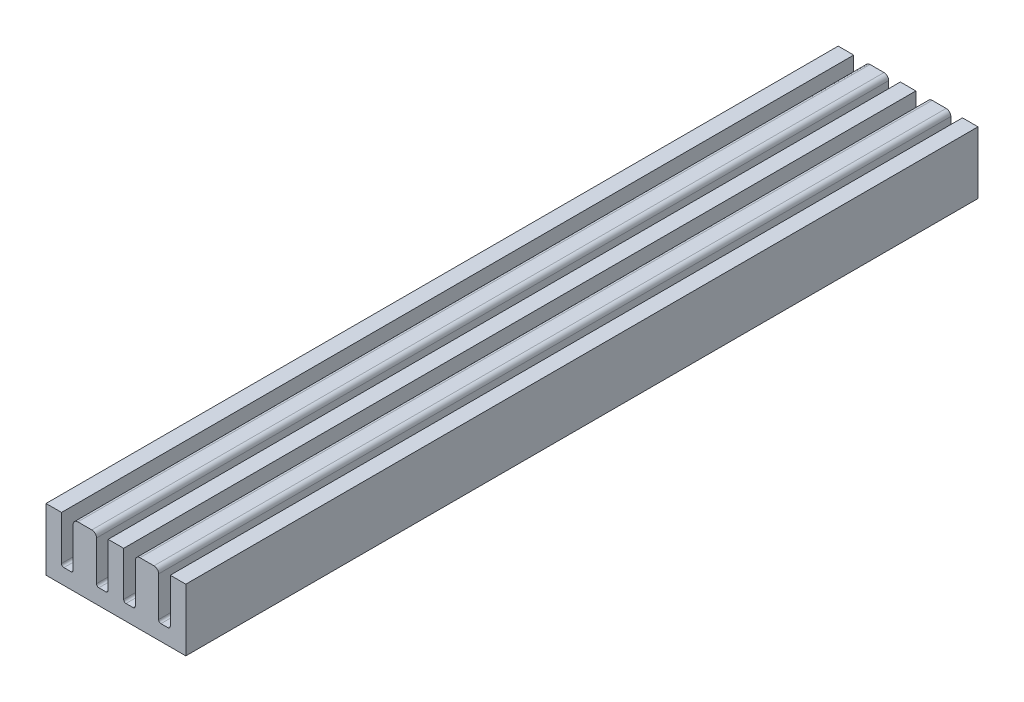
SolidWorks part; units mm, degrees
ref_plane "Plano frontal" through (0, 0, 0) normal (0, 0, 1) x (1, 0, 0)
ref_plane "Plano superior" through (0, 0, 0) normal (0, 1, 0) x (1, 0, 0)
ref_plane "Plano direito" through (0, 0, 0) normal (1, 0, 0) x (0, 0, -1)
sketch "Esboço1" plane through (0, 0, 0) normal (0, 0, 1) x (1, 0, 0)
  line L0 (-3.5, -37.8704) -> (-3.8019, -37.8704)
  line L1 (-2, -37.8704) -> (-2, -31.8704)
  line L2 (-3.5, -37.8704) -> (-5, -37.8704)
  line L3 (-0.5, -31.8704) -> (-3.5, -31.8704)
  line L4 (-2, -31.8704) -> (-2, -37.8704)
  line L5 (-0.5, -37.8704) -> (-3.5, -37.8704)
  line L6 (-3.5, -31.8704) -> (-3.5, -37.8704)
  line L7 (3, -37.8704) -> (1, -37.8704)
  line L8 (-2, -31.8704) -> (-2, -37.8704)
  line L9 (3, -31.8704) -> (3, -37.8704)
  line L10 (1, -31.8704) -> (3, -31.8704)
  line L11 (-3.5, -37.8704) -> (-3.5, -37.5685)
  line L12 (1, -37.8704) -> (1, -31.8704)
  line L13 (-5, -37.8704) -> (-5, -31.8704)
  line L14 (-5, -31.8704) -> (-7, -31.8704)
  line L15 (-7, -31.8704) -> (-7, -37.8704)
  line L16 (-7, -37.8704) -> (-5, -37.8704)
  line L17 (-0.5, -37.8704) -> (-0.5, -37.5685)
  line L18 (-0.5, -31.8704) -> (-0.5, -37.8704)
  line L19 (-0.5, -37.8704) -> (1, -37.8704)
  line L20 (-0.5, -37.8704) -> (-0.1981, -37.8704)
  line L22 (4.5, -37.8704) -> (4.1981, -37.8704)
  line L23 (4.5, -37.8704) -> (3, -37.8704)
  line L24 (4.5, -31.8704) -> (4.5, -37.8704)
  line L25 (4.5, -37.8704) -> (4.5, -37.5685)
  line L26 (11, -37.8704) -> (9, -37.8704)
  line L27 (11, -31.8704) -> (11, -37.8704)
  line L28 (9, -31.8704) -> (11, -31.8704)
  line L29 (9, -37.8704) -> (9, -31.8704)
  line L30 (7.5, -37.8704) -> (7.5, -37.5685)
  line L31 (6, -31.8704) -> (6, -37.8704)
  line L32 (7.5, -31.8704) -> (7.5, -37.8704)
  line L33 (4.5, -37.8704) -> (7.5, -37.8704)
  line L34 (6, -31.8704) -> (6, -37.8704)
  line L35 (4.5, -31.8704) -> (7.5, -31.8704)
  line L36 (7.5, -37.8704) -> (9, -37.8704)
  line L37 (6, -37.8704) -> (6, -31.8704)
  line L38 (7.5, -37.8704) -> (7.8019, -37.8704)
  line L39 (-7, -37.8704) -> (11, -37.8704)
  line L40 (-7, -37.8704) -> (-7, -39.8704)
  line L41 (-7, -39.8704) -> (11, -39.8704)
  line L42 (11, -37.8704) -> (11, -39.8704)
  arc A0 (-3.8019, -37.8704) -> (-3.5, -37.5685) centre (-3.8019, -37.5685) ccw
  arc A1 (0.6981, -37.8704) -> (1, -37.5685) centre (0.6981, -37.5685) ccw
  arc A2 (-4.6981, -37.8704) -> (-5, -37.5685) centre (-4.6981, -37.5685) cw
  arc A3 (-0.1981, -37.8704) -> (-0.5, -37.5685) centre (-0.1981, -37.5685) cw
  arc A4 (4.1981, -37.8704) -> (4.5, -37.5685) centre (4.1981, -37.5685) ccw
  arc A5 (8.6981, -37.8704) -> (9, -37.5685) centre (8.6981, -37.5685) ccw
  arc A6 (3.3019, -37.8704) -> (3, -37.5685) centre (3.3019, -37.5685) cw
  arc A7 (7.8019, -37.8704) -> (7.5, -37.5685) centre (7.8019, -37.5685) cw
  dimension "D1" = 1.5
  dimension "D2" = 2
  dimension "D4" = 2
  dimension "D5" = 1.5
  dimension "D6" = 6
extrude "Ressalto-extrusão1" add sketch "Esboço1" along normal blind 102 contours L3 L6 L5 L1 | L1 region at (-2.75, -34.8704, 0) region at (-1.25, -34.8704, 0)
extrude "Ressalto-extrusão3" add sketch "Esboço1<6>" along normal blind 102 contours L15 L16 L13 L14 | L2 A2 L13 | A0 L0 L6 | L19 A3 L17 | A1 L19 L12 | L12 L7 L9 L10 | L23 A6 L9 | A4 L22 L24 | L35 L24 L33 L31 | L35 L31 L33 L30 L32 | L36 A7 L30 | A5 L36 L29 | L29 L26 L27 L28 region at (-3.5674, -37.8029, 0) region at (-4.9326, -37.8029, 0) region at (-0.4326, -37.8029, 0) region at (-6, -34.8704, 0) region at (0.9326, -37.8029, 0) region at (2, -34.8704, 0) region at (3.0674, -37.8029, 0) region at (10, -34.8704, 0) region at (8.9326, -37.8029, 0) region at (4.4326, -37.8029, 0) region at (5.25, -34.8704, 0) region at (7.5674, -37.8029, 0) region at (6.75, -34.8704, 0)
sketch "Esboço1<6>" plane through (0, 0, 0) normal (0, 0, 1) x (1, 0, 0) same geometry as "Esboço1"
extrude "Ressalto-extrusão4" add sketch "Esboço1<7>" along normal blind 102 contours L42 L26 L39 L36 L33 L22 L23 L7 L19 L5 L0 L2 L16 L40 L41 region at (2, -38.8704, 0)
sketch "Esboço1<7>" plane through (0, 0, 0) normal (0, 0, 1) x (1, 0, 0) same geometry as "Esboço1"
fillet "Filete3" radius 0.6 4 edges at (7.5, -31.8704, 51) (4.5, -31.8704, 51) (-0.5, -31.8704, 51) (-3.5, -31.8704, 51)
